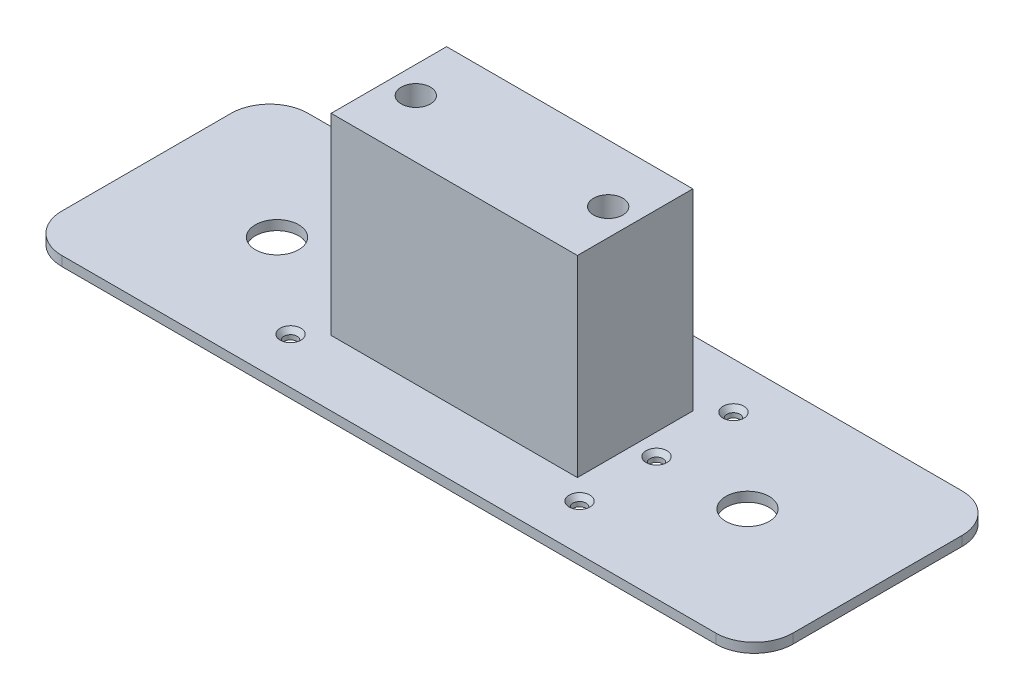
SolidWorks part; units mm, degrees
material "ABS"
ref_plane "Front" through (0, 0, 0) normal (0, 0, 1) x (1, 0, 0)
ref_plane "Top" through (0, 0, 0) normal (0, 1, 0) x (1, 0, 0)
ref_plane "Right" through (0, 0, 0) normal (1, 0, 0) x (0, 0, -1)
sketch "Sketch1" plane through (0, 0, 0) normal (0, 1, 0) x (1, 0, 0)
  line L1 (-60.325, 20.32) -> (60.325, 20.32)
  line L2 (-60.325, 20.32) -> (-60.325, -20.32)
  line L3 (-60.325, -20.32) -> (60.325, -20.32)
  line L4 (60.325, 20.32) -> (60.325, -20.32)
  line L5 (-60.325, 20.32) -> (60.325, -20.32) construction
  line L6 (-60.325, -20.32) -> (60.325, 20.32) construction
  point P0 (0, 0)
  dimension "D1" = 120.65
  dimension "D2" = 40.64
extrude "Boss-Extrude1" add sketch "Sketch1" along normal blind 1.5875
fillet "Fillet1" radius 6.35 4 edges at (-60.325, 0.7937, 20.32) (-60.325, 0.7937, -20.32) (60.325, 0.7937, -20.32) (60.325, 0.7937, 20.32)
sketch "Sketch2" plane through (0, 1.5875, 0) normal (0, 1, 0) x (1, 0, 0)
  line L1 (-20.32, 9.525) -> (20.32, 9.525)
  line L2 (-20.32, 9.525) -> (-20.32, -9.525)
  line L3 (-20.32, -9.525) -> (20.32, -9.525)
  line L4 (20.32, 9.525) -> (20.32, -9.525)
  line L5 (-20.32, 9.525) -> (20.32, -9.525) construction
  line L6 (-20.32, -9.525) -> (20.32, 9.525) construction
  point P0 (0, 0)
  dimension "D1" = 40.64
  dimension "D2" = 19.05
extrude "Boss-Extrude2" add sketch "Sketch2" along normal blind 31.75
sketch "Sketch3" plane through (0, 33.3375, 0) normal (0, 1, 0) x (1, 0, 0)
  line L0 (-15.875, 0) -> (15.875, 0) construction
  point P4 (0, 0)
  point P6 (-15.875, 0)
  point P7 (15.875, 0)
  dimension "D1" = 31.75
hole_wizard "#10 Clearance Hole1" positions "Sketch4" profile "Sketch5" hole size "#10" standard "ANSI Inch"
sketch "Sketch4" plane through (0, 33.3375, 0) normal (0, 1, 0) x (1, 0, 0)
  point P0 (-15.875, 0)
  point P3 (15.875, 0)
sketch "Sketch5" plane through (-15.875, 33.3375, 0) normal (1, 0, 0) x (0, 0, 1)
  line L0 (0, 0) -> (0, 26.8499)
  line L1 (0, 26.8499) -> (2.413, 25.4)
  line L2 (2.413, 25.4) -> (2.413, 0)
  line L5 (2.413, 0) -> (0, 0)
  line L10 (0, 26.8499) -> (-2.413, 25.4) construction
  line L11 (0, -6.35) -> (0, 107.95) construction
  dimension "Hole Dia." = 4.826
  dimension "Hole Depth" = 25.4
  dimension "Drill Angle" = 118
sketch "Sketch10" plane through (0, 0, 0) normal (0, -1, 0) x (1, 0, 0)
  line L1 (0, -50) -> (0, 50) construction
  circle A0 centre (23.85, -12.7) radius 1.0795 construction
  circle A1 centre (23.85, 12.7) radius 1.0795 construction
  circle A2 centre (23.85, 0) radius 1.0795 construction
  point P0 (23.85, 12.7)
  point P1 (23.85, 0)
  point P2 (23.85, -12.7)
  point P18 (-23.85, -12.7)
  point P19 (-23.85, 0)
  point P20 (-23.85, 12.7)
hole_wizard "#2 Clearance Hole1" positions "Sketch11" profile "Sketch12" hole size "#2" standard "ANSI Inch" end condition through all
sketch "Sketch11" plane through (0, 1.5875, 0) normal (0, 1, 0) x (1, 0, 0)
  point P0 (-23.85, 12.7)
  point P3 (-23.85, 0)
  point P6 (-23.85, -12.7)
  point P9 (23.85, -12.7)
  point P12 (23.85, 0)
  point P15 (23.85, 12.7)
sketch "Sketch12" plane through (-23.85, 1.5875, -12.7) normal (1, 0, 0) x (0, 0, 1)
  line L0 (0, 0) -> (0, 1.5875)
  line L1 (0, 1.5875) -> (1.0795, 1.5875)
  line L2 (1.0795, 1.5875) -> (1.0795, 0.8275)
  line L3 (1.0795, 0.8275) -> (1.7145, 0)
  line L5 (1.7145, 0) -> (0, 0)
  line L6 (-1.0795, 0.8275) -> (-1.7145, 0) construction
  line L11 (0, -6.35) -> (0, 107.95) construction
  dimension "Thru Hole Dia." = 2.159
  dimension "Thru Hole Depth" = 1.5875
  dimension "Near C'Sink Dia." = 3.429
  dimension "Near C'Sink Angle" = 75
sketch "Sketch13" plane through (0, 0, 0) normal (0, -1, 0) x (-1, 0, 0)
  line L0 (0, 50) -> (0, -50) construction
  circle A0 centre (38.825, 0.0428) radius 3.843 construction
  circle A1 centre (38.825, 0.0428) radius 3.575
  circle A2 centre (-38.825, 0.0428) radius 3.843 construction
  circle A3 centre (-38.825, 0.0428) radius 3.575
  dimension "D1" = 7.15
extrude "Cut-Extrude1" cut sketch "Sketch13" against normal through all
